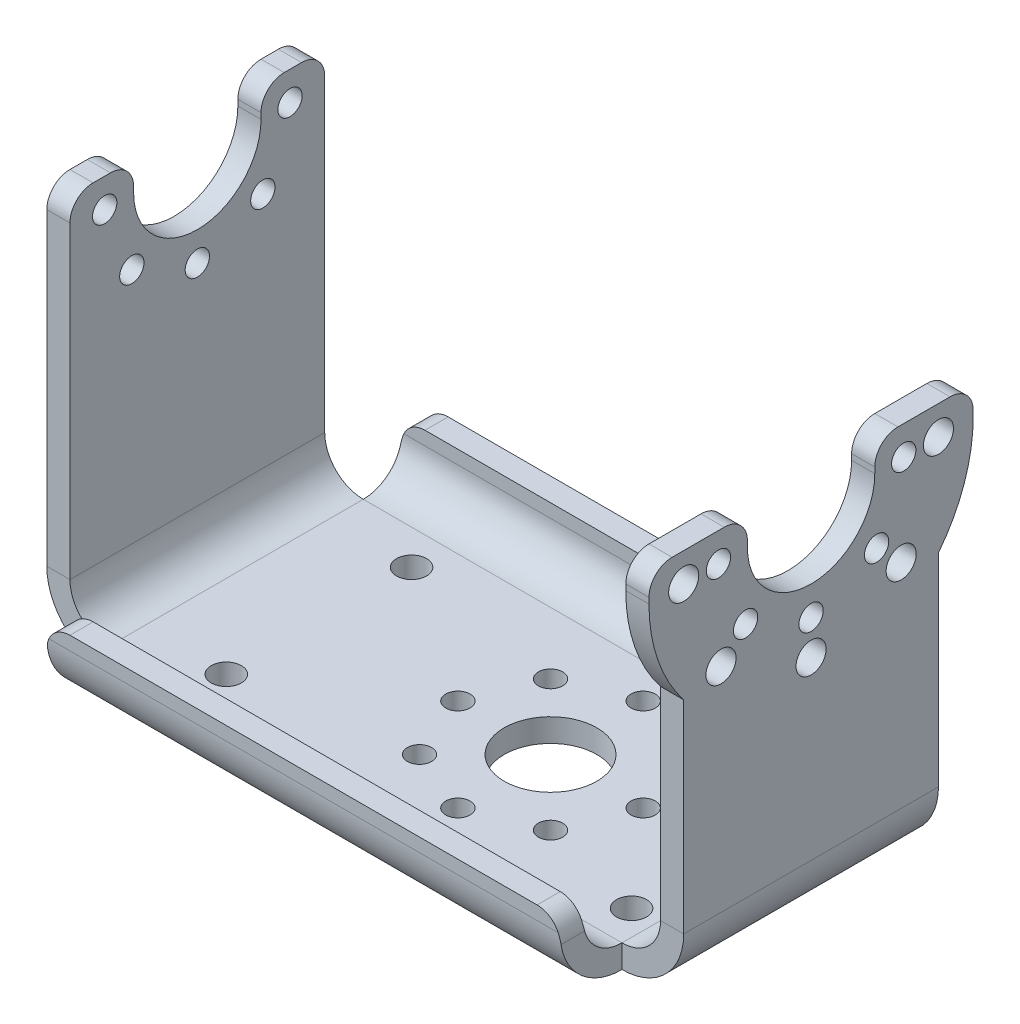
SolidWorks part; units mm, degrees
note: The reader was unsure of these and kept them because the rebuilt part matched: bend radius of "BaseBend1", "BaseBend2"; flange length of "Edge-Flange1".
material "2024 Alloy (SN)"
ref_plane "Front Plane" through (0, 0, 0) normal (0, 0, 1) x (1, 0, 0)
ref_plane "Top Plane" through (0, 0, 0) normal (0, 1, 0) x (1, 0, 0)
ref_plane "Right Plane" through (0, 0, 0) normal (1, 0, 0) x (0, 0, -1)
sketch "Sketch1" plane through (0, 0, 0) normal (0, 0, 1) x (1, 0, 0)
  line L0 (-26.55, 32) -> (-26.55, 0)
  line L1 (-26.55, 0) -> (24.45, 0)
  line L2 (24.45, 0) -> (24.45, 32)
  dimension "D1" = 24.45
  dimension "D2" = 32
  dimension "D3" = 26.55
sheet metal parameters "Sheet-Metal1" thickness 2 parameters "D1"=3.33
base flange "Base-Flange1" sketch "Sketch1" end condition mid plane depth 22 reverse direction no thickness 2 reverse thickness direction no bend radius 3.33
bend "BaseBend1" bend radius 3.33 bend angle 90 parameters "D5"=1
bend "BaseBend2" bend radius 3.33 bend angle 90 parameters "D5"=2
sketch "Sketch5" plane through (0, 0, 0) normal (0, 1, 0) x (1, 0, 0)
  line L0 (-26.55, 0) -> (24.45, 0) construction
  circle A0 centre (3.95, 0) radius 4
  circle A1 centre (18.95, 8) radius 1.3
  circle A2 centre (18.95, -8) radius 1.3
  circle A3 centre (-16.05, -8) radius 1.3
  circle A4 centre (-16.05, 8) radius 1.3
  circle A5 centre (-4.05, 0) radius 1.05
  circle A6 centre (-1.7069, 5.6569) radius 1.05
  circle A7 centre (3.95, 8) radius 1.05
  circle A8 centre (9.6069, 5.6569) radius 1.05
  circle A9 centre (11.95, 0) radius 1.05
  circle A10 centre (9.6069, -5.6569) radius 1.05
  circle A11 centre (3.95, -8) radius 1.05
  circle A12 centre (-1.7069, -5.6569) radius 1.05
  dimension "D1" = 8
  dimension "D2" = 3.95
  dimension "D3" = 2.6
  dimension "D4" = 2.1
  dimension "D5" = 8
  dimension "D6" = 15
  dimension "D7" = 8
  dimension "D8" = 35
  dimension "D9" = 8
  dimension "D10" = 8
  dimension "D11" = 8
extrude "Cut-Extrude1" cut sketch "Sketch5" against normal blind 10
sketch "Sketch6" plane through (0, 0, 0) normal (1, 0, 0) x (0, 0, -1)
  line L2 (4.05, 32) -> (-4.05, 32)
  line L3 (4.05, 32) -> (4.05, 29.5)
  line L4 (-11, 32) -> (11, 32) construction
  line L5 (-4.05, 32) -> (-4.05, 29.5)
  arc A0 (-4.05, 29.5) -> (4.05, 29.5) centre (0, 29.5) ccw
  circle A1 centre (0, 21.5) radius 1.05
  circle A2 centre (-5.6569, 23.8431) radius 1.05
  circle A3 centre (-8, 29.5) radius 1.05
  circle A4 centre (-5.6569, 35.1569) radius 1.05
  circle A5 centre (0, 37.5) radius 1.05
  circle A6 centre (5.6569, 35.1569) radius 1.05
  circle A7 centre (8, 29.5) radius 1.05
  circle A8 centre (5.6569, 23.8431) radius 1.05
  dimension "D1" = 2.5
  dimension "D2" = 10.5
  dimension "D3" = 2.1
  dimension "D4" = 4.05
extrude "Cut-Extrude2" cut sketch "Sketch6" against normal through all and the other way through all
sketch "Sketch7" plane through (-28.55, 0, 0) normal (-1, 0, 0) x (0, 0, 1)
  line L0 (-4.05, 32) -> (-11, 32) construction
  line L1 (-5.5, 32) -> (5.5, 32)
  line L2 (-5.5, 32) -> (-5.5, 29.5)
  line L4 (5.5, 32) -> (5.5, 29.5)
  arc A0 (-5.5, 29.5) -> (5.5, 29.5) centre (0, 29.5) ccw
  dimension "D1" = 11
extrude "Cut-Extrude3" cut sketch "Sketch7" against normal blind 10
fillet "Fillet1" radius 2 6 edges at (-27.55, 32, 11) (-27.55, 32, -11) (25.45, 32, 11) (25.45, 32, -11) (-27.55, 32, 5.5) (-27.55, 32, -5.5)
sketch "Sketch8" plane through (0, 0, 11) normal (0, 0, 1) x (1, 0, 0)
  line L1 (-23.22, 0) -> (21.12, 0)
  line L2 (-23.22, 0) -> (-23.22, -2)
  line L3 (-23.22, -2) -> (21.12, -2)
  line L4 (21.12, 0) -> (21.12, -2)
edge flange "Edge-Flange1" sketch "Sketch11" flange angle 90 flange length 4.5 flange position bend outside bend radius 3.33 thickness 2 parameters "D6"=10
sketch "Sketch11" plane through (0, 0, 11) normal (0, 0, 1) x (1, 0, 0)
  line L0 (-23.22, 0) -> (21.12, 0) construction
  line L1 (-23.22, 0) -> (21.12, 0)
  line L2 (-23.22, 0) -> (-23.22, 4.5)
  line L3 (-23.22, 4.5) -> (21.12, 4.5)
  line L4 (21.12, 4.5) -> (21.12, 0)
bend "EdgeBend1" bend radius 3.33 bend angle 90 parameters "D5"=3
fillet "Fillet2" radius 2 2 edges at (-23.22, 4.5, 15.33) (21.12, 4.5, 15.33)
mirror "Mirror1" about plane through (0, 0, 0) normal (0, 0, 1) of "Fillet2", "Edge-Flange1"
bend "MirrorBend1" bend radius 3.33 bend angle 90 parameters "D5"=4
sketch "Sketch14" plane through (26.45, 0, 0) normal (1, 0, 0) x (0, 0, -1)
  line L0 (4.05, 32) -> (9, 32) construction
  line L1 (-14, 29.5) -> (14, 29.5)
  line L2 (-14, 29.5) -> (-14, 32)
  line L3 (-14, 32) -> (14, 32)
  line L4 (14, 29.5) -> (14, 32)
  arc A0 (-14, 29.5) -> (14, 29.5) centre (0, 29.5) ccw
  arc A1 (-8.9058, 32) -> (8.9058, 32) centre (0, 29.5) ccw
  arc M7 (-9, 32) -> (-11, 30) centre (-9, 30) ccw
  line M8 (-11, 30) -> (-11, 3.33)
  line M10 (11, 3.33) -> (11, 30)
  arc M11 (11, 30) -> (9, 32) centre (9, 30) ccw
  line M12 (9, 32) -> (4.05, 32)
  dimension "D1" = 18.5
  dimension "D2" = 28
extrude "Boss-Extrude2" add sketch "Sketch14" against normal blind 2 contours L1 A0 M8 | A1 L1 A0 M8 M10 | L3 L2 L1 M8 M7 | A1 L3 L1 M7 M8 | L1 L4 L3 M11 M10 | A0 L1 M10 | A1 L1 M10 M11 M12
fillet "Fillet4" radius 2 2 edges at (25.45, 32, 14) (25.45, 32, -14)
sketch "Sketch15" plane through (26.45, 0, 0) normal (1, 0, 0) x (0, 0, -1)
  line L0 (0, 32) -> (0, 0) construction
  circle A0 centre (0, 18.5) radius 1.3
  arc A1 (-4.05, 29.5) -> (4.05, 29.5) centre (0, 29.5) ccw construction
  circle A2 centre (-7.7782, 21.7218) radius 1.3
  circle A3 centre (-11, 29.5) radius 1.3
  circle A4 centre (-7.7782, 37.2782) radius 1.3
  circle A5 centre (0, 40.5) radius 1.3
  circle A6 centre (7.7782, 37.2782) radius 1.3
  circle A7 centre (11, 29.5) radius 1.3
  circle A8 centre (7.7782, 21.7218) radius 1.3
  point P7 (0, 29.5)
  point P25 (0, 29.5)
  dimension "D1" = 11
  dimension "D2" = 2.6
  dimension "D3" = 8
extrude "Cut-Extrude5" cut sketch "Sketch15" against normal blind 2
sketch "Sketch16" plane through (24.45, 0, 0) normal (-1, 0, 0) x (0, 0, 1)
  line L1 (-5.5, 29.5) -> (5.5, 29.5)
  line L2 (-5.5, 29.5) -> (-5.5, 36.1626)
  line L3 (-5.5, 36.1626) -> (5.5, 36.1626)
  line L4 (5.5, 29.5) -> (5.5, 36.1626)
  circle A0 centre (0, 29.5) radius 5.5
  line M11 (-4.05, 32) -> (-12, 32)
  line M21 (12, 32) -> (4.05, 32)
  line M23 (4.05, 32) -> (4.05, 29.5)
  arc M24 (4.05, 29.5) -> (-4.05, 29.5) centre (0, 29.5) cw
  line M25 (-4.05, 29.5) -> (-4.05, 32)
  dimension "D1" = 11
extrude "Cut-Extrude6" cut sketch "Sketch16" against normal blind 10 contours L1 A0 M24 | A0 L1 M21 M11 M25 M23 | A0 L1 M11 M25 | A0 L2 M11 | A0 L4 L3 L2 M21 M11 | L1 A0 M21 M23 | A0 L4 M21
fillet "Fillet5" radius 2 2 edges at (25.45, 32, 5.5) (25.45, 32, -5.5)
flat pattern "Flat-Pattern1" [suppressed]
sketch "Bend-Lines1" plane through (0, 0, 0) normal (0, 1, 0) x (-1, 0, 0)
  line L0 (26.6208, 11) -> (26.6208, -11) construction
  line L1 (-24.5208, -11) -> (-24.5208, 11) construction
  line L2 (26.6208, 11) -> (26.6208, -11) construction
  line L3 (-24.5208, -11) -> (-24.5208, 11) construction
  line L4 (23.22, -14.4008) -> (-21.12, -14.4008) construction
  line L5 (-21.12, 14.4008) -> (23.22, 14.4008) construction
  line L6 (23.22, -14.4008) -> (-21.12, -14.4008) construction
  line L7 (-21.12, 14.4008) -> (23.22, 14.4008) construction
sketch3d "Bounding-Box1" [suppressed]
  line L0 (32.1416, 7.9715, 0) -> (-83.1415, 7.9716, 0) construction
  line L1 (32.1415, -29.9716, 0) -> (-83.1416, -29.9715, 0) construction
  line L2 (32.1416, 7.9715, 0) -> (32.1415, -29.9716, 0) construction
  line L3 (-83.1415, 7.9716, 0) -> (-83.1416, -29.9715, 0) construction
bend of the flat pattern "Flatten-<BaseBend1>1"
bend of the flat pattern "Flatten-<BaseBend2>1"
bend of the flat pattern "Flatten-<EdgeBend1>1"
bend of the flat pattern "Flatten-<MirrorBend1>1"
